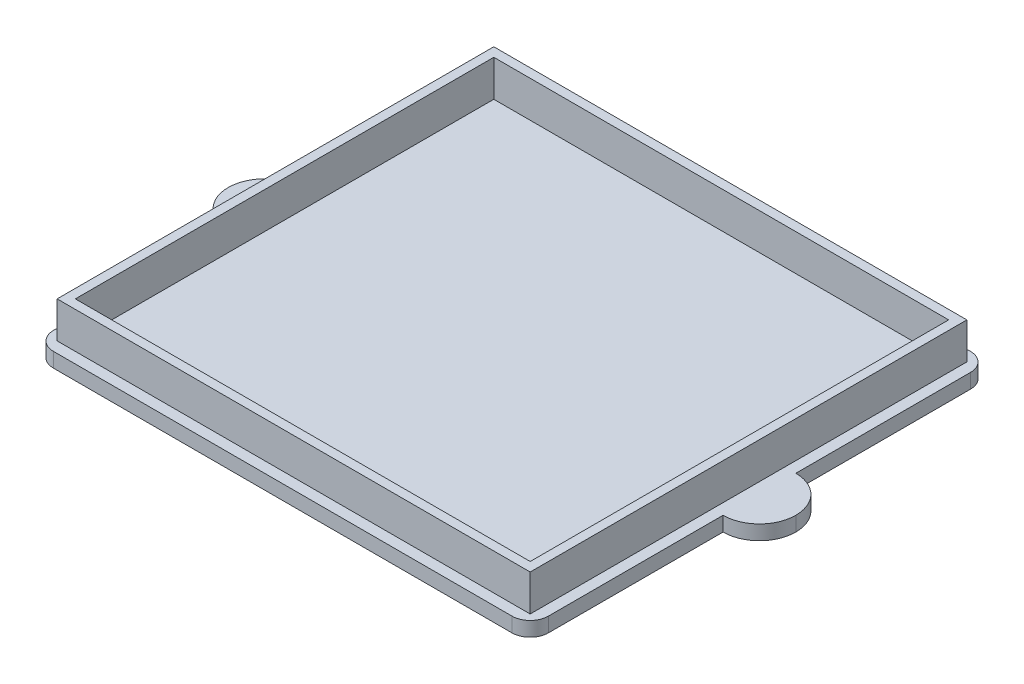
SolidWorks part; units mm, degrees
ref_plane "Front Plane" through (0, 0, 0) normal (0, 0, 1) x (1, 0, 0)
ref_plane "Top Plane" through (0, 0, 0) normal (0, 1, 0) x (1, 0, 0)
ref_plane "Right Plane" through (0, 0, 0) normal (1, 0, 0) x (0, 0, -1)
sketch "Sketch1" plane through (0, 0, 0) normal (0, 1, 0) x (1, 0, 0)
  line L1 (-68, 63) -> (68, 63)
  line L2 (-68, 63) -> (-68, 39.9792)
  line L3 (-68, -63) -> (68, -63)
  line L4 (68, 63) -> (68, 39.9792)
  line L5 (-68, 63) -> (68, -63) construction
  line L6 (-68, -63) -> (68, 63) construction
  line L10 (0, 106.6321) -> (0, -106.6321) construction
  line L14 (-68, -10) -> (-68, -63)
  line L15 (68, -10) -> (68, -63)
  line L16 (68, 10) -> (68, 39.9792)
  line L17 (-68, 10) -> (-68, 39.9792)
  line L18 (-78, 10) -> (-68, 10)
  line L19 (78, -10) -> (68, -10)
  line L20 (78, -10) -> (78, 10)
  line L21 (78, 10) -> (68, 10)
  line L23 (-78, -10) -> (-78, 10)
  line L24 (-78, -10) -> (-68, -10)
  point P0 (0, 0)
  point P9 (-50, 0)
  point P10 (68, 0)
  point P14 (0, 0)
  dimension "D1" = 126
  dimension "D2" = 136
  dimension "D3" = 10
  dimension "D4" = 20
extrude "Boss-Extrude1" add sketch "Sketch1" along normal blind 4
sketch "Sketch3" plane through (0, 4, 0) normal (0, 1, 0) x (1, 0, 0)
  line L0 (-68, 63) -> (-68, 10) construction
  line L1 (-65, 60) -> (65, 60)
  line L2 (-65, 60) -> (-65, -60)
  line L3 (-65, -60) -> (65, -60)
  line L4 (65, 60) -> (65, -60)
  line L5 (-65, 60) -> (65, -60) construction
  line L6 (-65, -60) -> (65, 60) construction
  line L7 (68, 63) -> (-68, 63) construction
  line L9 (-62.5, 57.5) -> (62.5, 57.5)
  line L10 (-62.5, 57.5) -> (-62.5, -57.5)
  line L11 (-62.5, -57.5) -> (62.5, -57.5)
  line L12 (62.5, 57.5) -> (62.5, -57.5)
  line L13 (-62.5, 57.5) -> (62.5, -57.5) construction
  line L14 (-62.5, -57.5) -> (62.5, 57.5) construction
  point P0 (0, 0)
  point P10 (0, 0)
  dimension "D1" = 3
  dimension "D2" = 3
  dimension "D3" = 2.5
  dimension "D4" = 2.5
extrude "Boss-Extrude2" add sketch "Sketch3" along normal blind 10
fillet "Fillet1" radius 5 4 edges at (-68, 2, -63) (68, 2, -63) (68, 2, 63) (-68, 2, 63)
fillet "Fillet2" radius 10 4 edges at (78, 2, -10) (78, 2, 10) (-78, 2, 10) (-78, 2, -10)
